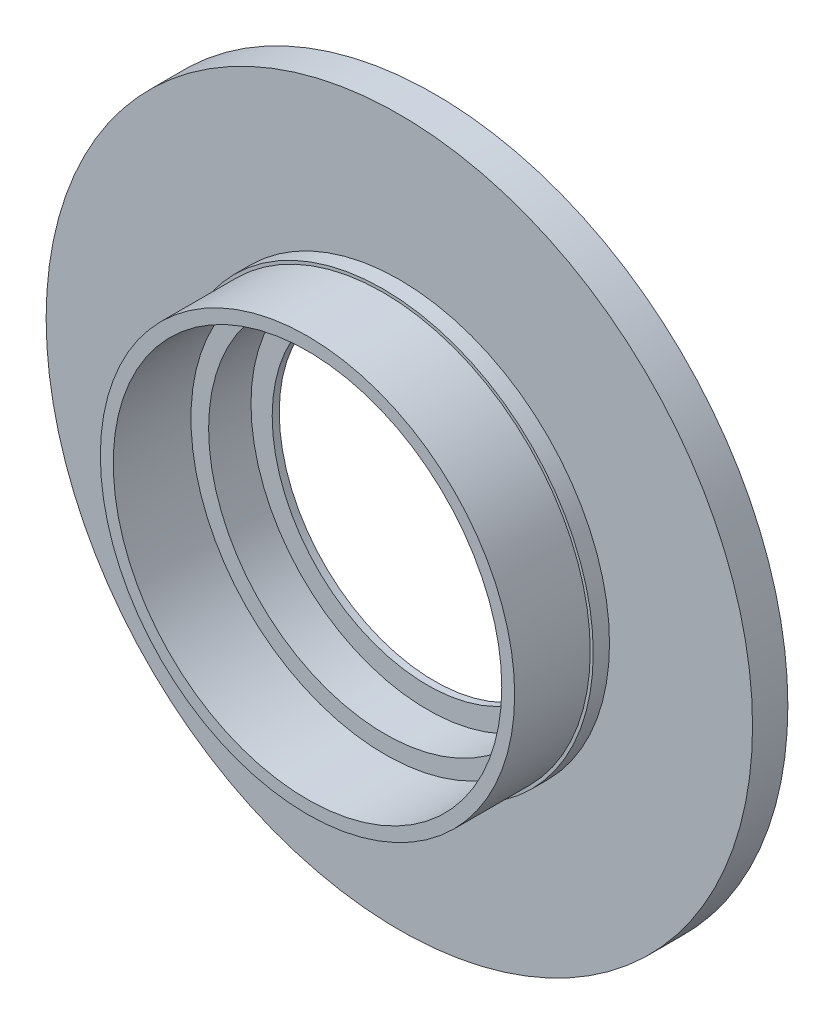
SolidWorks part; units mm, degrees
ref_plane "Front Plane" through (0, 0, 0) normal (0, 0, 1) x (1, 0, 0)
ref_plane "Top Plane" through (0, 0, 0) normal (0, 1, 0) x (1, 0, 0)
ref_plane "Right Plane" through (0, 0, 0) normal (1, 0, 0) x (0, 0, -1)
sketch "Sketch1" plane through (0, 0, 0) normal (0, 0, 1) x (1, 0, 0)
  circle A0 centre (0, 0) radius 50
  circle A1 centre (0, 0) radius 45
  circle A2 centre (0, 0) radius 29.325
  circle A3 centre (0, 0) radius 27.5
  circle A4 centre (0, 0) radius 22.5
  circle A5 centre (0, 0) radius 22
  dimension "D1" = 100
  dimension "D2" = 90
  dimension "D3" = 58.65
  dimension "D4" = 55
  dimension "D5" = 45
  dimension "D6" = 44
extrude "Boss-Extrude1" add sketch "Sketch1" along normal blind 5 contours A0 A1 | A1 A2 | A2 A3 | A3 A4 | A4 A5 region at (-48.5858, 0, 0) region at (-43.7272, 0, 0) region at (-28.4956, 0, 0) region at (-26.7222, 0, 0) region at (-22.4364, 0, 0)
extrude "Boss-Extrude2" add sketch "Sketch1<3>" along normal blind 18 contours A2 A3 region at (-28.4956, 0, 0)
sketch "Sketch1<3>" plane through (0, 0, 0) normal (0, 0, 1) x (1, 0, 0) same geometry as "Sketch1"
sketch "Sketch2" plane through (0, 0, 5) normal (0, 0, 1) x (1, 0, 0)
  circle A0 centre (0, 0) radius 29.75
  circle A1 centre (0, 0) radius 29.325 construction
  circle A2 centre (0, 0) radius 29.325
  dimension "D1" = 59.5
extrude "Boss-Extrude3" add sketch "Sketch2" along normal blind 2.3
sketch "Sketch3" plane through (0, 0, 5) normal (0, 0, 1) x (1, 0, 0)
  circle A0 centre (0, 0) radius 27.5
  circle A1 centre (0, 0) radius 25
  dimension "D1" = 55
  dimension "D2" = 50
extrude "Boss-Extrude4" add sketch "Sketch3" along normal blind 2
sketch "Sketch4" plane through (0, 0, 5) normal (0, 0, 1) x (1, 0, 0)
  circle A0 centre (0, 0) radius 22 construction
  circle A1 centre (0, 0) radius 25 construction
  circle A2 centre (0, 0) radius 22
  circle A3 centre (0, 0) radius 25
extrude "Cut-Extrude1" cut sketch "Sketch4" against normal blind 4
